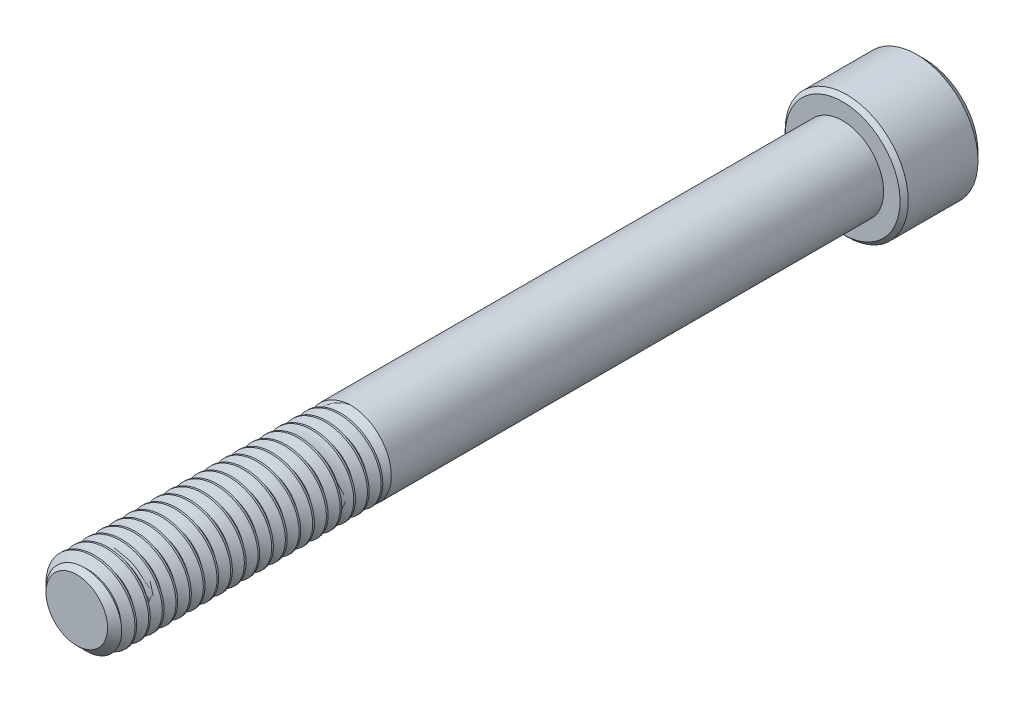
SolidWorks part; units mm, degrees
material "Cast Alloy Steel"
ref_plane "Front Plane" through (0, 0, 0) normal (0, 0, 1) x (1, 0, 0)
ref_plane "Top Plane" through (0, 0, 0) normal (0, 1, 0) x (1, 0, 0)
ref_plane "Right Plane" through (0, 0, 0) normal (1, 0, 0) x (0, 0, -1)
sketch "Sketch1" plane through (0, 0, 0) normal (0, 0, 1) x (1, 0, 0)
  line L0 (0, 4.7625) -> (0, -4.7625) construction
  circle A0 centre (0, 0) radius 4.7625
  dimension "OD" = 9.525
extrude "Extrude1" add sketch "Sketch1" against normal blind 88.9
sketch "Sketch2" plane through (0, 0, 0) normal (0, 0, 1) x (1, 0, 0)
  circle A0 centre (0, 0) radius 4.7625 construction
  circle A1 centre (0, 0) radius 4.7625
curve "Helix/Spiral1" pitch 1.5875 height 34.925 turns 22 parameters "pitch"=1.5875
chamfer "Chamfer3" distance 1.1906 angle 45 1 edges at (4.7625, 0, 0)
sketch "Sketch3" plane through (0, 0, 0) normal (1, 0, 0) x (0, 0, -1)
  line L0 (-1.3891, 4.7625) -> (-0.7938, 3.7314)
  line L1 (-0.7938, 3.7314) -> (-0.5953, 3.7314)
  line L2 (-0.5953, 3.7314) -> (0, 4.7625)
  line L3 (-1.3891, 4.7625) -> (0, 4.7625)
  line L4 (-0.6945, 4.7625) -> (-0.6945, 3.7314) construction
  line L5 (-1.0914, 4.2469) -> (-0.2977, 4.2469) construction
  line L6 (0, 4.7625) -> (0, -4.7625) construction
  dimension "D1" = 0.1984
  dimension "D2" = 0.7937
  dimension "D3" = 60
sweep "Cut-Sweep1" cut profiles "Sketch3" path "Helix/Spiral1"
sketch "Sketch5" plane through (0, 0, 0) normal (1, 0, 0) x (0, 0, -1)
  line L1 (88.9, 4.7625) -> (31.75, 4.7625)
  line L2 (88.9, 4.7625) -> (88.9, 0)
  line L3 (88.9, 0) -> (31.75, 0)
  line L4 (31.75, 4.7625) -> (31.75, 0) construction
  line L6 (0, 0) -> (9.9695, 0) construction
  line L8 (31.75, 4.7625) -> (26.9875, 0)
  line L9 (26.9875, 0) -> (31.75, 0)
  line L10 (88.9, -4.7625) -> (88.9, 4.7625) construction
  dimension "D1" = 45
  dimension "Thread min" = 31.75
revolve "partially thread" add sketch "Sketch5" angle 360 about L6
sketch "Sketch6" plane through (0, 0, -88.9) normal (0, 0, -1) x (-1, 0, 0)
  circle A0 centre (0, 0) radius 7.1438
  dimension "head dia" = 14.2875
extrude "Extrude2" add sketch "Sketch6" along normal blind 9.525
sketch "Sketch7" plane through (0, 0, -98.425) normal (0, 0, -1) x (-1, 0, 0)
  line L1 (0, 4.5827) -> (-3.9688, 2.2914)
  line L2 (-3.9688, 2.2914) -> (-3.9688, -2.2914)
  line L3 (-3.9688, -2.2914) -> (0, -4.5827)
  line L4 (0, -4.5827) -> (3.9688, -2.2914)
  line L5 (3.9688, -2.2914) -> (3.9688, 2.2914)
  line L6 (3.9688, 2.2914) -> (0, 4.5827)
  circle A0 centre (0, 0) radius 3.9688 construction
  dimension "hex dia" = 7.9375
extrude "Cut-Extrude1" cut sketch "Sketch7" against normal blind 5.9531
sketch "Sketch8" plane through (0, 0, -98.425) normal (0, 0, -1) x (-1, 0, 0)
  circle A0 centre (0, 0) radius 4.5827
extrude "Cut-Extrude2" cut sketch "Sketch8" against normal blind 0.9525 draft 45
chamfer "Chamfer1" distance 0.9525 angle 45 1 edges at (-7.1438, 0, -98.425)
chamfer "Chamfer2" distance 0.4763 angle 45 1 edges at (-7.1438, 0, -88.9)
sketch "Sketch9" plane through (0, 0, 0) normal (1, 0, 0) x (0, 0, -1)
  line L0 (0, 4.7625) -> (0, -4.7625) construction
  line L1 (8.7312, 4.7625) -> (8.7312, -4.7625) construction
  line L2 (88.9, 7.1437) -> (88.9, -7.1437) construction
  line L3 (98.425, 7.1437) -> (98.425, -7.1437) construction
  line L4 (98.425, 0) -> (0, 0) construction
  line L5 (61.6852, 4.7625) -> (61.6852, -4.7625) construction
  dimension "D1" = 8.7312
  dimension "D2" = 9.525
  dimension "D3" = 14.2875
  dimension "D4" = 88.9
  dimension "Thread Length" = 61.6852
equation "\"D3@Helix/Spiral1\" = \"Thread min@Sketch5\"+(\"pitch@Helix/Spiral1\"*2)"
equation "\"D1@Sketch3\" = \"pitch@Helix/Spiral1\"*.125"
equation "\"D2@Sketch3\" = \"pitch@Helix/Spiral1\"*.5"
equation "\"D1@Cut-Extrude1\" = \"hex dia@Sketch7\"*.75"
equation "\"D1@Chamfer1\" = \"head depth@Extrude2\"/10"
equation "\"D1@Sketch9\" = \"pitch@Helix/Spiral1\"*5.5"
equation "\"D1@Chamfer2\" = \"D1@Chamfer1\"/2"
equation "\"D1@Cut-Extrude2\" = \"D1@Chamfer2\"*2"
equation "\"D1@Chamfer3\" = \"pitch@Helix/Spiral1\"*.750"
equation "\"D2@Sketch9\" = \"head depth@Extrude2\""
equation "\"D3@Sketch9\" = \"head dia@Sketch6\""
equation "\"D4@Sketch9\" = \"screw length@Extrude1\""
